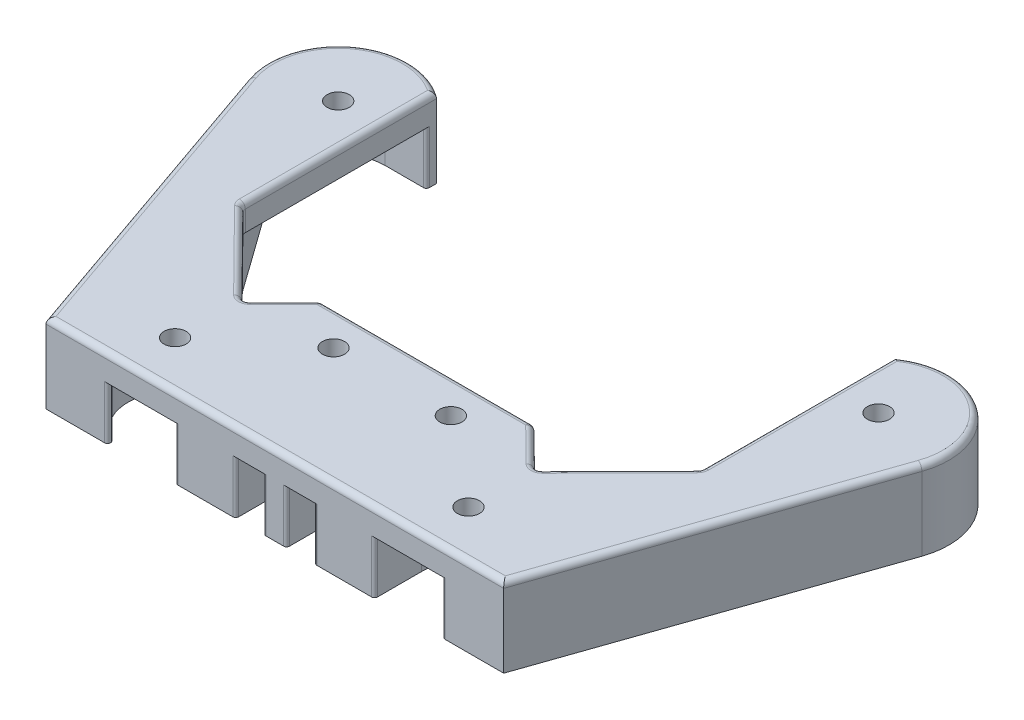
SolidWorks part; units mm, degrees
ref_plane "Front Plane" through (0, 0, 0) normal (0, 0, 1) x (1, 0, 0)
ref_plane "Top Plane" through (0, 0, 0) normal (0, 1, 0) x (1, 0, 0)
ref_plane "Right Plane" through (0, 0, 0) normal (1, 0, 0) x (0, 0, -1)
sketch "Sketch2" plane through (0, 0, 0) normal (0, 1, 0) x (1, 0, 0)
  line L0 (-19.8438, 0) -> (19.8438, 0) construction
  line L1 (0, 0) -> (0, 9.525) construction
  line L2 (0, 9.525) -> (7.9375, 9.525) construction
  line L3 (0, 9.525) -> (-7.9375, 9.525) construction
  line L4 (0, 9.525) -> (0, 38.7629) construction
  line L5 (0, 38.7629) -> (-36.5442, 38.7629) construction
  line L6 (0, 38.7629) -> (36.5442, 38.7629) construction
  line L7 (14.4174, 14.2875) -> (19.7894, 8.9801)
  line L8 (-19.7894, 8.9801) -> (-14.4174, 14.2875)
  line L9 (-30.9563, 46.4766) -> (-30.9562, 20.2828)
  line L10 (-30.9562, 20.2828) -> (-19.7894, 8.9801)
  line L11 (-19.8438, -6.35) -> (19.8438, -6.35)
  line L15 (30.9563, 46.4766) -> (30.9562, 20.2828)
  line L16 (30.9562, 20.2828) -> (19.7894, 8.9801)
  line L17 (-19.8438, -6.35) -> (-30.9562, -6.35)
  line L18 (-30.9562, -6.35) -> (-45.5418, 35.6374)
  line L19 (19.8438, -6.35) -> (30.9562, -6.35)
  line L20 (30.9562, -6.35) -> (45.5418, 35.6374)
  line L21 (-14.4174, 14.2875) -> (14.4174, 14.2875)
  circle A0 centre (-19.8438, 0) radius 1.5
  circle A1 centre (19.8438, 0) radius 1.5
  circle A2 centre (-7.9375, 9.525) radius 1.5
  circle A3 centre (7.9375, 9.525) radius 1.5
  circle A4 centre (-19.8438, 0) radius 6 construction
  circle A5 centre (-7.9375, 9.525) radius 6 construction
  circle A6 centre (7.9375, 9.525) radius 6 construction
  circle A7 centre (19.8438, 0) radius 6 construction
  circle A8 centre (-36.5442, 38.7629) radius 1.5
  circle A9 centre (36.5442, 38.7629) radius 1.5
  circle A10 centre (-36.5442, 38.7629) radius 6 construction
  circle A11 centre (36.5442, 38.7629) radius 6 construction
  arc A12 (-30.9563, 46.4766) -> (-45.5418, 35.6374) centre (-36.5442, 38.7629) ccw
  arc A13 (45.5418, 35.6374) -> (30.9563, 46.4766) centre (36.5442, 38.7629) ccw
  circle A14 centre (-36.5442, 38.7629) radius 6.35 construction
  circle A15 centre (36.5442, 38.7629) radius 6.35 construction
  circle A20 centre (-19.8438, 0) radius 6.35 construction
  circle A21 centre (-7.9375, 9.525) radius 6.35 construction
  circle A22 centre (7.9375, 9.525) radius 6.35 construction
  circle A23 centre (19.8438, 0) radius 6.35 construction
  point P3 (0, -6.35)
  point P4 (0, 0)
  point P24 (0, 14.2875)
  dimension "D2" = 3
  dimension "D5" = 12
  dimension "D8" = 19.05
  dimension "D9" = 12.7
  dimension "D12" = 6.35
  dimension "D1" = 9.525
  dimension "D3" = 39.6875
  dimension "D4" = 7.9375
  dimension "D6" = 29.2379
  dimension "D7" = 36.5442
  dimension "D10" = 5.588
  dimension "D11" = 26.1937
  dimension "D14" = 61.9125
  dimension "D15" = 20.6375
extrude "Boss-Extrude1" add sketch "Sketch2" along normal blind 10.7315
sketch "Sketch3" plane through (0, 0, 0) normal (0, -1, 0) x (1, 0, 0)
  line L1 (-1.5875, -9.525) -> (-1.5875, 6.35)
  line L6 (-36.5442, -45.1129) -> (-30.9563, -45.1129)
  line L7 (-30.9563, -46.4766) -> (-30.9562, -20.2828) construction
  line L8 (-41.7061, -35.0647) -> (-21.0504, -6.2343)
  line L9 (-30.9562, -26.4134) -> (-14.6819, -3.6983)
  line L10 (-16.1857, -2.6208) -> (-40.2023, -36.1421) construction
  line L11 (-30.9563, -45.1129) -> (-30.9562, -26.4134)
  line L13 (-13.4937, 0) -> (-13.4938, 6.35)
  line L14 (-19.8438, 6.35) -> (19.8438, 6.35) construction
  line L18 (-21.0504, -6.2343) -> (-18.0427, -8.3892) construction
  line L21 (-17.1938, 6.35) -> (-13.4938, 6.35)
  line L25 (-5.2875, -3.7544) -> (-5.2875, 6.35)
  line L27 (-5.2875, 6.35) -> (-1.5875, 6.35)
  line L29 (-3.4474, -14.0151) -> (-3.7197, -14.2875)
  line L34 (0, 0) -> (0, -14.2875) construction
  line L36 (-3.7197, -14.2875) -> (-12.1376, -14.2875)
  line L37 (21.0504, -6.2343) -> (18.0427, -8.3892) construction
  line L38 (16.1857, -2.6208) -> (40.2023, -36.1421) construction
  line L40 (3.4474, -14.0151) -> (3.7197, -14.2875)
  line L41 (5.2875, 6.35) -> (1.5875, 6.35)
  line L42 (5.2875, -3.7544) -> (5.2875, 6.35)
  line L43 (17.1938, 6.35) -> (13.4938, 6.35)
  line L45 (13.4937, 0) -> (13.4938, 6.35)
  line L46 (30.9562, -45.1129) -> (30.9562, -26.4134)
  line L47 (30.9562, -26.4134) -> (14.6819, -3.6983)
  line L48 (41.7061, -35.0647) -> (21.0504, -6.2343)
  line L49 (36.5442, -45.1129) -> (30.9562, -45.1129)
  line L50 (1.5875, -9.525) -> (1.5875, 6.35)
  line L51 (-19.8438, 6.35) -> (-17.1938, 6.35)
  line L52 (19.8438, 6.35) -> (17.1938, 6.35)
  line L57 (3.7197, -14.2875) -> (12.1376, -14.2875)
  line L58 (14.4174, -14.2875) -> (-14.4174, -14.2875) construction
  arc A0 (-19.8438, 6.35) -> (-21.0504, -6.2343) centre (-19.8438, 0) ccw
  circle A2 centre (-7.9375, -9.525) radius 6.35 construction
  arc A4 (-5.2875, -3.7544) -> (-12.1376, -14.2875) centre (-7.9375, -9.525) ccw
  circle A5 centre (-7.9375, -9.525) radius 4.5 construction
  circle A12 centre (-36.5442, -38.7629) radius 6.35 construction
  arc A13 (-41.7061, -35.0647) -> (-36.5442, -45.1129) centre (-36.5442, -38.7629) ccw
  circle A16 centre (19.8438, 0) radius 4.5 construction
  circle A17 centre (-19.8438, 0) radius 6.35 construction
  arc A30 (-14.6819, -3.6983) -> (-13.4937, 0) centre (-19.8438, 0) ccw
  circle A31 centre (-36.5442, -38.7629) radius 4.5 construction
  circle A32 centre (-19.8438, 0) radius 4.5 construction
  arc A33 (-3.4474, -14.0151) -> (-1.5875, -9.525) centre (-7.9375, -9.525) ccw
  circle A34 centre (36.5442, -38.7629) radius 4.5 construction
  circle A35 centre (7.9375, -9.525) radius 4.5 construction
  arc A36 (3.4474, -14.0151) -> (1.5875, -9.525) centre (7.9375, -9.525) cw
  arc A37 (14.6819, -3.6983) -> (13.4937, 0) centre (19.8438, 0) cw
  arc A38 (41.7061, -35.0647) -> (36.5442, -45.1129) centre (36.5442, -38.7629) cw
  arc A39 (5.2875, -3.7544) -> (12.1376, -14.2875) centre (7.9375, -9.525) cw
  arc A41 (19.8438, 6.35) -> (21.0504, -6.2343) centre (19.8438, 0) cw
  dimension "D1" = 9
  dimension "D2" = 45
extrude "Cut-Extrude1" cut sketch "Sketch3" against normal blind 7.1742 and the other way through all
fillet "Fillet1" radius 0.3969 20 edges at (30.9562, 3.5871, -45.1129) (13.4938, 3.5871, 6.35) (19.0145, 3.5871, -9.7457) (5.2875, 3.5871, 6.35) (1.5875, 3.5871, 6.35) (-1.5875, 3.5871, 6.35) (-5.2875, 3.5871, 6.35) (-30.9563, 3.5871, -45.1129) (-19.0145, 3.5871, -9.7457) (-13.4938, 3.5871, 6.35) (-3.7197, 3.5871, -14.2875) (3.7197, 3.5871, -14.2875)
sketch "Sketch4" plane through (0, 7.1742, 0) normal (0, -1, 0) x (1, 0, 0)
  circle A0 centre (-19.8438, 0) radius 3
  circle A1 centre (-36.5442, -38.7629) radius 3
  circle A2 centre (-7.9375, -9.525) radius 3
  circle A3 centre (7.9375, -9.525) radius 3
  circle A4 centre (19.8438, 0) radius 3
  circle A5 centre (36.5442, -38.7629) radius 3
  circle A6 centre (36.5442, -38.7629) radius 1.5 construction
  circle A7 centre (19.8438, 0) radius 1.5 construction
  circle A8 centre (7.9375, -9.525) radius 1.5 construction
  circle A9 centre (-7.9375, -9.525) radius 1.5 construction
  circle A10 centre (-36.5442, -38.7629) radius 1.5 construction
  circle A11 centre (-19.8438, 0) radius 1.5 construction
  circle A12 centre (36.5442, -38.7629) radius 1.5
  circle A13 centre (19.8438, 0) radius 1.5
  circle A14 centre (7.9375, -9.525) radius 1.5
  circle A15 centre (-7.9375, -9.525) radius 1.5
  circle A16 centre (-36.5442, -38.7629) radius 1.5
  circle A17 centre (-19.8438, 0) radius 1.5
  dimension "D1" = 6
extrude "Boss-Extrude3" add sketch "Sketch4" along normal blind 0.7937
chamfer "Chamfer1" distance 0.7937 angle 45 6 edges at (36.5442, 7.1742, -35.7629) (19.8438, 7.1742, 3) (7.9375, 7.1742, -6.525) (-7.9375, 7.1742, -12.525) (-36.5442, 7.1742, -41.7629) (-19.8438, 7.1742, -3)
fillet "Fillet2" radius 0.7937 6 edges at (-14.4174, 5.3658, -14.2875) (14.4174, 5.3658, -14.2875)
fillet "Fillet3" radius 0.7937 18 edges at (-38.249, 10.7315, -14.6437) (30.9563, 10.7315, -33.5427) (30.8967, 10.7315, -20.3072) (-30.9563, 10.7315, -33.5427) (-30.8967, 10.7315, -20.3072) (-25.5372, 10.7315, -14.7978) (-19.7874, 10.7315, -9.3089) (-16.9371, 10.7315, -11.7982) (16.9371, 10.7315, -11.7982) (19.7874, 10.7315, -9.3089) (42.2257, 10.7315, -46.408) (-42.2257, 10.7315, -46.408) (25.5372, 10.7315, -14.7978) (38.249, 10.7315, -14.6437) (-14.393, 10.7315, -14.228) (0, 10.7315, -14.2875) (14.393, 10.7315, -14.228) (0, 10.7315, 6.35)
